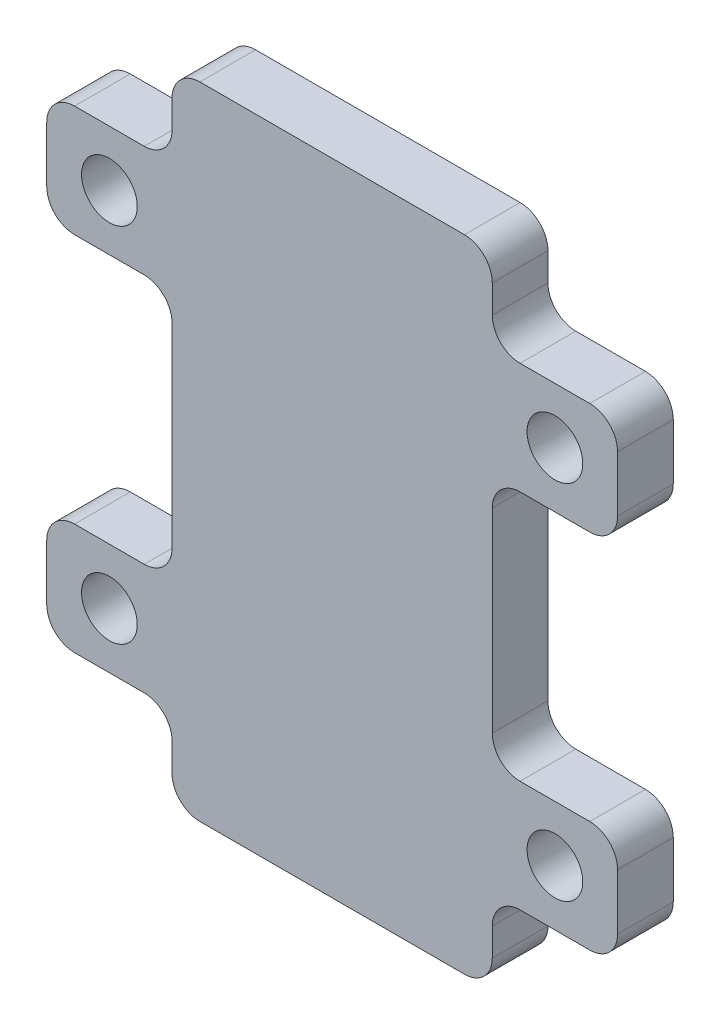
SolidWorks part; units mm, degrees
ref_plane "Front Plane" through (0, 0, 0) normal (0, 0, 1) x (1, 0, 0)
ref_plane "Top Plane" through (0, 0, 0) normal (0, 1, 0) x (1, 0, 0)
ref_plane "Right Plane" through (0, 0, 0) normal (1, 0, 0) x (0, 0, -1)
sketch "Sketch1" plane through (0, 0, 0) normal (0, 0, 1) x (1, 0, 0)
  line L0 (-2.875, 11) -> (-2.875, 10.5)
  line L1 (-3.375, 10) -> (-4.625, 10)
  line L2 (-5.125, 9.5) -> (-5.125, 8.5)
  line L3 (-4.625, 8) -> (-3.375, 8)
  line L4 (-2.875, 7.5) -> (-2.875, 4)
  line L5 (-3.375, 3.5) -> (-4.625, 3.5)
  line L6 (-5.125, 3) -> (-5.125, 2)
  line L7 (-4.625, 1.5) -> (-3.375, 1.5)
  line L8 (-2.875, 1) -> (-2.875, 0.5)
  line L12 (-4, 10) -> (-4, 8) construction
  line L13 (0, -6.5439) -> (0, 23.2179) construction
  line L14 (-2.375, 0) -> (2.375, 0)
  line L15 (-2.375, 11.5) -> (2.375, 11.5)
  line L29 (-4, 3.5) -> (-4, 1.5) construction
  line L30 (4, 3.5) -> (4, 1.5) construction
  line L31 (4, 10) -> (4, 8) construction
  line L32 (2.875, 1) -> (2.875, 0.5)
  line L33 (4.625, 1.5) -> (3.375, 1.5)
  line L34 (5.125, 3) -> (5.125, 2)
  line L35 (3.375, 3.5) -> (4.625, 3.5)
  line L36 (2.875, 7.5) -> (2.875, 4)
  line L37 (4.625, 8) -> (3.375, 8)
  line L38 (5.125, 9.5) -> (5.125, 8.5)
  line L39 (3.375, 10) -> (4.625, 10)
  line L40 (2.875, 11) -> (2.875, 10.5)
  arc A0 (-2.875, 10.5) -> (-3.375, 10) centre (-3.375, 10.5) cw
  arc A1 (-4.625, 10) -> (-5.125, 9.5) centre (-4.625, 9.5) ccw
  arc A2 (-5.125, 8.5) -> (-4.625, 8) centre (-4.625, 8.5) ccw
  arc A3 (-3.375, 8) -> (-2.875, 7.5) centre (-3.375, 7.5) cw
  arc A4 (-2.875, 4) -> (-3.375, 3.5) centre (-3.375, 4) cw
  arc A5 (-4.625, 3.5) -> (-5.125, 3) centre (-4.625, 3) ccw
  arc A6 (-5.125, 2) -> (-4.625, 1.5) centre (-4.625, 2) ccw
  arc A7 (-3.375, 1.5) -> (-2.875, 1) centre (-3.375, 1) cw
  arc A8 (-2.875, 0.5) -> (-2.375, 0) centre (-2.375, 0.5) ccw
  arc A9 (-2.375, 11.5) -> (-2.875, 11) centre (-2.375, 11) ccw
  circle A20 centre (-4, 9) radius 0.5
  circle A21 centre (-4, 2.5) radius 0.5
  circle A22 centre (4, 2.5) radius 0.5
  circle A23 centre (4, 9) radius 0.5
  arc A24 (2.375, 11.5) -> (2.875, 11) centre (2.375, 11) cw
  arc A25 (2.875, 0.5) -> (2.375, 0) centre (2.375, 0.5) cw
  arc A26 (3.375, 1.5) -> (2.875, 1) centre (3.375, 1) ccw
  arc A27 (5.125, 2) -> (4.625, 1.5) centre (4.625, 2) cw
  arc A28 (4.625, 3.5) -> (5.125, 3) centre (4.625, 3) cw
  arc A29 (2.875, 4) -> (3.375, 3.5) centre (3.375, 4) ccw
  arc A30 (3.375, 8) -> (2.875, 7.5) centre (3.375, 7.5) ccw
  arc A31 (5.125, 8.5) -> (4.625, 8) centre (4.625, 8.5) cw
  arc A32 (4.625, 10) -> (5.125, 9.5) centre (4.625, 9.5) cw
  arc A33 (2.875, 10.5) -> (3.375, 10) centre (3.375, 10.5) ccw
  point P30 (0, 0)
  point P36 (0, 0)
  point P96 (0, 11.5)
  dimension "D1" = 0.5
  dimension "D3" = 1
  dimension "D2" = 6.5
  dimension "D4" = 8
  dimension "D5" = 2.25
  dimension "D6" = 2.5
  dimension "D7" = 2
extrude "Boss-Extrude1" add sketch "Sketch1" along normal blind 1
